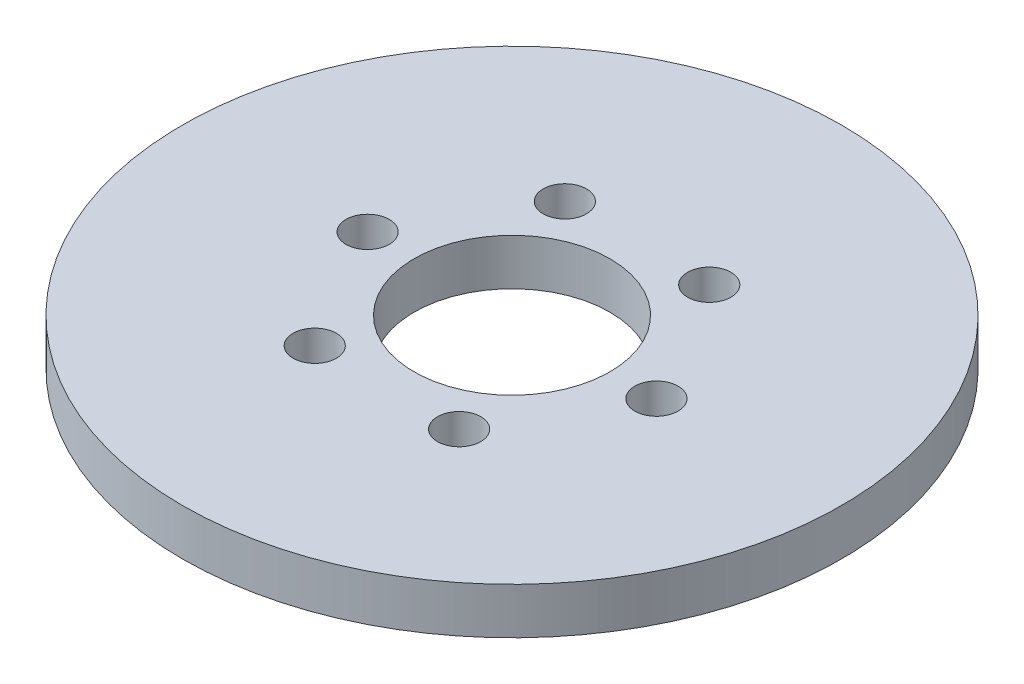
SolidWorks part; units mm, degrees
ref_plane "Front Plane" through (0, 0, 0) normal (0, 0, 1) x (1, 0, 0)
ref_plane "Top Plane" through (0, 0, 0) normal (0, 1, 0) x (1, 0, 0)
ref_plane "Right Plane" through (0, 0, 0) normal (1, 0, 0) x (0, 0, -1)
sketch "Sketch1" plane through (0, 0, 0) normal (0, 1, 0) x (1, 0, 0)
  circle A0 centre (0, 0) radius 92.5
  dimension "FLANGE_OD" = 185
extrude "Boss-Extrude1" add sketch "Sketch1" along normal blind 13
sketch "Sketch2" plane through (0, 0, 0) normal (0, 1, 0) x (1, 0, 0)
  circle A0 centre (0, 0) radius 27.5
  dimension "BORE_D" = 55
extrude "Cut-Extrude1" cut sketch "Sketch2" along normal through all
sketch "Sketch3" plane through (0, 13, 0) normal (0, 1, 0) x (1, 0, 0)
  circle A0 centre (0, 0) radius 40.5314 construction
  circle A1 centre (-40.5314, 0) radius 6.0765
  dimension "BOLT_D" = 12.153
  dimension "BOLT_PCD" = 81.0627
extrude "Cut-Extrude2" cut sketch "Sketch3" against normal blind 10.4558
pattern_circular "CirPattern1" count 6 over 360 about axis through (0, 0, 0) along (0, 1, 0) of "Cut-Extrude2"
